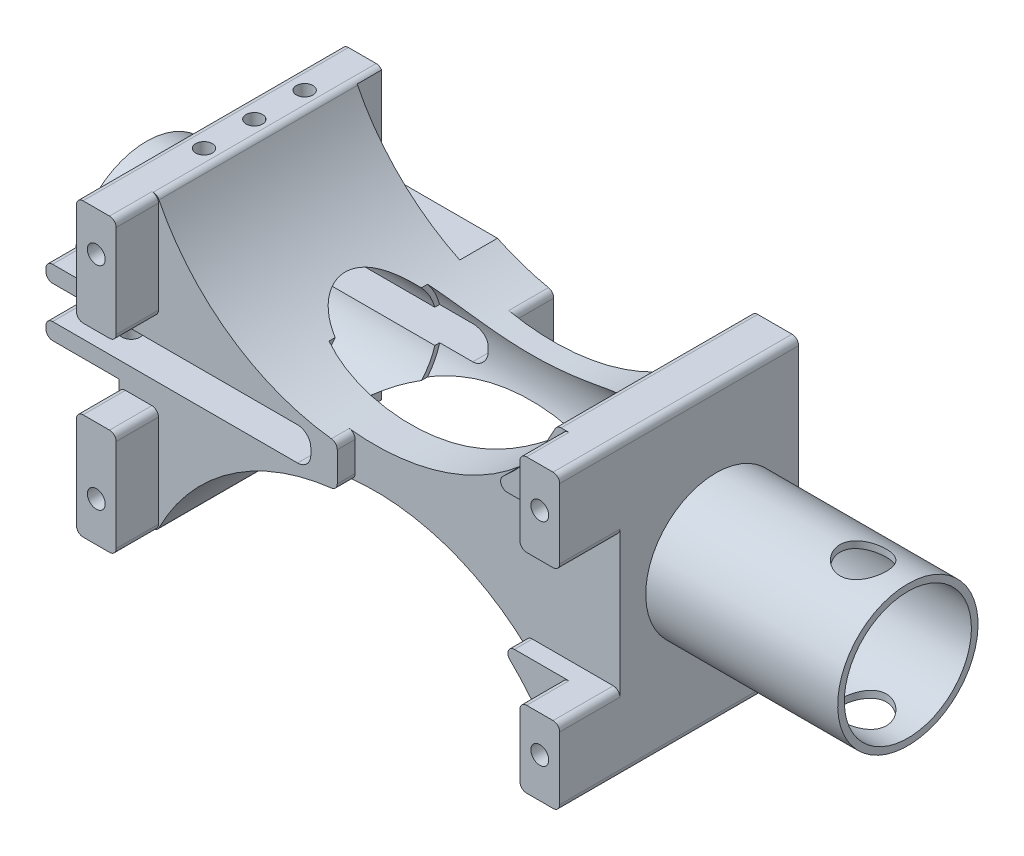
SolidWorks part; units mm, degrees
material "6061 合金"
ref_plane "前视基准面" through (0, 0, 0) normal (0, 0, 1) x (1, 0, 0)
ref_plane "上视基准面" through (0, 0, 0) normal (0, 1, 0) x (1, 0, 0)
ref_plane "右视基准面" through (0, 0, 0) normal (1, 0, 0) x (0, 0, -1)
other "Configuration Table"
sketch "草图1" plane through (0, 0, 0) normal (0, 0, 1) x (1, 0, 0)
  line L0 (0, 0) -> (36.5, 0) construction
  line L1 (-36.5, 22) -> (36.5, 22)
  line L2 (-36.5, 22) -> (-36.5, -22)
  line L3 (-36.5, -22) -> (36.5, -22)
  line L4 (36.5, 22) -> (36.5, -22)
  line L5 (-36.5, 22) -> (36.5, -22) construction
  line L6 (-36.5, -22) -> (36.5, 22) construction
  circle A0 centre (-0.5, 36.5) radius 33.5
  circle A1 centre (-0.5, -36.5) radius 33.5
  point P0 (0, 0)
  dimension "D4" = 67
  dimension "D5" = 37
  dimension "D1" = 44
  dimension "D2" = 73
  dimension "D3" = 73
extrude "凸台-拉伸1" add sketch "草图1" along normal blind 40 contours L3 A1 L4 L1 A0 L2
sketch "草图2" plane through (36.5, 0, 0) normal (1, 0, 0) x (0, 0, -1)
  line L1 (0, 22) -> (0, -22) construction
  circle A0 centre (-22.8, 0) radius 9.6
  dimension "D1" = 19.2
  dimension "D2" = 22.8
sketch "草图3" plane through (-36.5, 0, 0) normal (-1, 0, 0) x (0, 0, 1)
  circle A0 centre (22.8, 0) radius 8.9
  dimension "D1" = 17.8
extrude "切除-拉伸1" cut sketch "草图3" against normal through all
sketch "草图4" plane through (0, 0, 40) normal (0, 0, 1) x (1, 0, 0)
  line L0 (-7.5, -2.5) -> (-36.5, -2.5)
  line L1 (-7.5, -2.5) -> (-7.5, 2.5)
  line L2 (-36.5, -2.5) -> (-36.5, 2.5)
  line L3 (-7.5, 2.5) -> (-36.5, 2.5)
  line L4 (-7.5, -2.5) -> (-36.5, 2.5) construction
  line L5 (-36.5, -2.5) -> (-7.5, 2.5) construction
  line L6 (-36.5, 22) -> (-36.5, -22) construction
  point P1 (-22, 0)
  dimension "D1" = 5
  dimension "D2" = 29
extrude "切除-拉伸2" cut sketch "草图4" against normal through all
fillet "圆角1" radius 2 4 edges at (-7.5, -2.5, 7.1292) (-7.5, 2.5, 7.1292) (-7.5, -2.5, 35.6708) (-7.5, 2.5, 35.6708)
extrude "切除-拉伸3" cut sketch "草图2" against normal blind 51
sketch "草图5" plane through (0, 0, 0) normal (0, 0, -1) x (-1, 0, 0)
  line L0 (-36.5, 22) -> (-36.5, -22) construction
  line L1 (36.5, 22) -> (36.5, 2.5) construction
  line L2 (36.5, -2.5) -> (36.5, -22) construction
  circle A0 centre (-31.5, 10) radius 1.6
  circle A1 centre (-31.5, -10) radius 1.6
  circle A2 centre (33.5, 10) radius 1.6
  circle A3 centre (33.5, -10) radius 1.6
  dimension "D4" = 3.2
  dimension "D5" = 3.2
  dimension "D6" = 3.2
  dimension "D7" = 3.2
  dimension "D1" = 20
  dimension "D2" = 10
  dimension "D3" = 5
  dimension "D8" = 20
  dimension "D9" = 3
  dimension "D10" = 3
extrude "切除-拉伸4" [suppressed] cut sketch "草图5" against normal through all
sketch "草图6" plane through (0, 0, 0) normal (0, 0, -1) x (-1, 0, 0)
  line L0 (36.5, 22) -> (30.5, 22)
  line L1 (36.5, 22) -> (30.6993, 22) construction
  line L2 (30.5, 22) -> (30.5, 8.3)
  line L3 (30.5, 6.3) -> (11.32, 6.3)
  line L4 (11.32, 6.3) -> (11.32, 22)
  line L5 (11.32, 22) -> (30.5, 22)
  line L6 (0, 0) -> (13.8076, 0) construction
  line L7 (11.32, -22) -> (30.5, -22)
  line L8 (11.32, -6.3) -> (11.32, -22)
  line L9 (30.5, -6.3) -> (11.32, -6.3)
  line L10 (30.5, -22) -> (30.5, -8.3)
  line L11 (36.5, -22) -> (30.5, -22)
  arc A0 (30.5, -8.3) -> (30.5, -6.3) centre (30.5, -7.3) ccw
  arc A1 (30.5, 6.3) -> (30.5, 8.3) centre (30.5, 7.3) ccw
  line M16 (36.5, 22) -> (30.6993, 22)
  arc M17 (30.6993, 22) -> (-29.6993, 22) centre (0.5, 36.5) cw
  arc M21 (-29.6993, -22) -> (30.6993, -22) centre (0.5, -36.5) cw
  line M22 (30.6993, -22) -> (36.5, -22)
  dimension "D3" = 2
  dimension "D4" = 2
  dimension "D1" = 6
  dimension "D2" = 12.6
extrude "切除-拉伸5" cut sketch "草图6" against normal blind 10 contours L3 A1 L2 L4 M16 M17 | L10 A0 L9 L8 M21 M22
sketch "草图7" plane through (-36.5, 0, 0) normal (-1, 0, 0) x (0, 0, 1)
  circle A1 centre (22.8, 0) radius 11
  circle A2 centre (22.8, 0) radius 8.9
  dimension "D1" = 22
  dimension "D2" = 17.8
extrude "凸台-拉伸2" add sketch "草图7" along normal blind 13
chamfer "倒角1" distance 1.71 angle 45 1 edges at (-49.5, -8.9, 22.8)
sketch "草图9" plane through (-36.5, 0, 0) normal (1, 0, 0) x (0, 0, -1)
  line L1 (-19.4773, 2.5) -> (-41.3454, 2.5)
  line L2 (-19.4773, 2.5) -> (-19.4773, -2.5)
  line L3 (-19.4773, -2.5) -> (-41.3454, -2.5)
  line L4 (-41.3454, 2.5) -> (-41.3454, -2.5)
  line L5 (-19.4773, 2.5) -> (-41.3454, -2.5) construction
  line L6 (-19.4773, -2.5) -> (-41.3454, 2.5) construction
  point P0 (-30.4114, 0)
extrude "切除-拉伸6" cut sketch "草图9" against normal blind 13
sketch "草图10" plane through (-36.5, 0, 0) normal (-1, 0, 0) x (0, 0, 1)
  line L0 (22.8, 0) -> (46.6007, 0) construction
  line L1 (40, 5) -> (32.598, 5)
  line L2 (40, 22) -> (40, 2.5) construction
  line L3 (40, -5) -> (32.598, -5)
  line L4 (40, -2.5) -> (40, -22) construction
  line L5 (40, 5) -> (40, 2.5)
  line L6 (40, 2.5) -> (33.5121, 2.5)
  line L7 (33.5121, 2.5) -> (40, 2.5) construction
  line L8 (33.5121, -2.5) -> (40, -2.5)
  line L9 (40, -2.5) -> (40, -5)
  arc A1 (33.5121, 2.5) -> (33.5121, -2.5) centre (22.8, 0) ccw construction
  arc A2 (33.5121, 2.5) -> (32.598, 5) centre (22.8, 0) ccw
  arc A3 (32.598, -5) -> (33.5121, -2.5) centre (22.8, 0) ccw
  dimension "D1" = 5
  dimension "D2" = 5
extrude "凸台-拉伸6" add sketch "草图10" along normal blind 11
sketch "草图11" plane through (36.5, 0, 0) normal (1, 0, 0) x (0, 0, -1)
  circle A0 centre (-22.8, 0) radius 9.6
  circle A1 centre (-22.8, 0) radius 10.6
  dimension "D1" = 19.2
  dimension "D2" = 21.2
extrude "凸台-拉伸7" add sketch "草图11" along normal blind 29
sketch "草图12" plane through (0, 0, 0) normal (0, 1, 0) x (1, 0, 0)
  line L0 (65.5, -22.8) -> (36.5, -22.8) construction
  line L1 (65.5, -33.4) -> (65.5, -12.2) construction
  line L2 (36.5, -40) -> (36.5, 0) construction
  circle A0 centre (58.75, -22.8) radius 3.5
  dimension "D2" = 7
  dimension "D1" = 6.75
extrude "切除-拉伸7" cut sketch "草图12" against normal blind 13 and the other way blind 13
sketch "草图13" plane through (-36.5, 0, 0) normal (-1, 0, 0) x (0, 0, 1)
  line L1 (-4.3, -20) -> (4.3, -20)
  line L2 (-4.3, -20) -> (-4.3, 20)
  line L3 (-4.3, 20) -> (4.3, 20)
  line L4 (4.3, -20) -> (4.3, 20)
  line L5 (-4.3, -20) -> (4.3, 20) construction
  line L6 (-4.3, 20) -> (4.3, -20) construction
  arc A0 (31.3417, 2.5) -> (31.3417, -2.5) centre (22.8, 0) ccw construction
  point P0 (0, 0)
  dimension "D2" = 18.5
  dimension "D1" = 40
extrude "切除-拉伸8" cut sketch "草图13" against normal through all
sketch "草图14" plane through (-36.5, 0, 0) normal (-1, 0, 0) x (0, 0, 1)
  line L0 (4.3, 0.5) -> (4.3, -0.5) construction
  line L1 (2.3, -22) -> (6.3, -22)
  line L2 (2.3, -22) -> (2.3, -6.3)
  line L3 (2.3, 22) -> (6.3, 22)
  line L4 (6.3, -22) -> (6.3, -6.3)
  line L5 (2.3, -22) -> (6.3, 22) construction
  line L6 (2.3, 22) -> (6.3, -22) construction
  line L7 (40, 22) -> (0, 22) construction
  line L8 (4.3, 2.5) -> (4.3, 20) construction
  line L9 (6.3, 6.3) -> (6.3, 22)
  line L10 (2.3, -6.3) -> (6.3, -6.3)
  line L12 (2.3, 6.3) -> (6.3, 6.3)
  line L14 (2.3, -6.3) -> (6.3, 6.3) construction
  line L15 (2.3, 6.3) -> (6.3, -6.3) construction
  line L16 (2.3, 6.3) -> (2.3, 22)
  point P0 (4.3, 0)
  point P11 (4.3, 0)
  dimension "D1" = 2
  dimension "D2" = 12.6
extrude "切除-拉伸9" cut sketch "草图14" against normal blind 10
hole_wizard "M3x0.5 螺纹孔1" positions "草图15" profile "草图16" tap size "M3x0.5" standard "BSI"
sketch "草图15" plane through (0, 22, 0) normal (0, 1, 0) x (1, 0, 0)
  line L0 (-30.6993, -6.3) -> (-36.5, -6.3) construction
  point P0 (-33.2275, -15.2)
  point P2 (-33.2275, -22.8)
  point P4 (-33.2275, -30.4)
  dimension "D1" = 8.9
  dimension "D2" = 7.6
  dimension "D3" = 7.6
sketch "草图16" plane through (-33.2275, 22, 15.2) normal (1, 0, 0) x (0, 0, 1)
  line L0 (0, 0) -> (0, 6.7511)
  line L1 (0, 6.7511) -> (1.25, 6)
  line L2 (1.25, 6) -> (1.25, 0)
  line L5 (1.25, 0) -> (0, 0)
  line L10 (0, 6.7511) -> (-1.25, 6) construction
  line L11 (0, -6.35) -> (0, 107.95) construction
  dimension "螺纹孔钻头直径" = 2.5
  dimension "螺纹孔钻头深度" = 6
  dimension "导头角度" = 118
cosmetic thread "孔螺蚊线1" parameters "D1"=6, "D2"=3
cosmetic thread "孔螺蚊线2" parameters "D1"=6, "D2"=3
cosmetic thread "孔螺蚊线3" parameters "D1"=6, "D2"=3
sketch "草图17" plane through (36.5, 0, 0) normal (1, 0, 0) x (0, 0, -1)
  line L0 (-4.3, 20) -> (-4.3, -20) construction
  line L1 (1.7, 22) -> (-10.3, 22)
  line L2 (1.7, 22) -> (1.7, -22)
  line L3 (1.7, -22) -> (-10.3, -22)
  line L4 (-10.3, 22) -> (-10.3, -22)
  line L5 (1.7, 22) -> (-10.3, -22) construction
  line L6 (1.7, -22) -> (-10.3, 22) construction
  line L7 (-40, -22) -> (0, -22) construction
  circle A0 centre (-22.8, 0) radius 9.6 construction
  point P0 (-4.3, 0)
  dimension "D1" = 12.5
extrude "切除-拉伸10" cut sketch "草图17" against normal blind 37
sketch "草图18" plane through (0, 0, 10.3) normal (0, 0, -1) x (-1, 0, 0)
  line L0 (-36.5, 10.6) -> (-36.5, -10.6) construction
  line L2 (-26.8, 17.0845) -> (-26.8, -17.0845)
  line L4 (-22.8, 12.4301) -> (-22.8, -12.4301)
  line L5 (-26.6103, 16.8205) -> (-23.3983, -13.024) construction
  line L6 (-26.6103, -16.8205) -> (-23.3983, 13.024) construction
  arc A0 (-29.6993, 22) -> (0.5, 3) centre (0.5, 36.5) ccw construction
  arc A1 (0.5, -3) -> (-29.6993, -22) centre (0.5, -36.5) ccw construction
  arc A2 (-26.8, 17.0845) -> (-22.8, 12.4301) centre (0.5, 36.5) ccw
  arc A3 (-22.8, -12.4301) -> (-26.8, -17.0845) centre (0.5, -36.5) ccw
  point P0 (-24.8, 0)
  dimension "D1" = 13.7
extrude "凸台-拉伸8" add sketch "草图18" along normal blind 3
fillet "圆角2" radius 1 4 edges at (22.8, 12.4301, 8.8) (26.8, 17.0845, 8.8) (22.8, -12.4301, 8.8) (26.8, -17.0845, 8.8)
sketch "草图19" plane through (36.5, 0, 0) normal (1, 0, 0) x (0, 0, -1)
  line L1 (-42.7, 9.5) -> (-37.3, 9.5)
  line L2 (-42.7, 9.5) -> (-42.7, -10.5)
  line L3 (-42.7, -10.5) -> (-37.3, -10.5)
  line L4 (-37.3, 9.5) -> (-37.3, -10.5)
  line L5 (-42.7, 9.5) -> (-37.3, -10.5) construction
  line L6 (-42.7, -10.5) -> (-37.3, 9.5) construction
  circle A0 centre (-22.8, 0) radius 9.6 construction
  point P0 (-40, -0.5)
  dimension "D1" = 20
  dimension "D2" = 14.5
extrude "切除-拉伸11" cut sketch "草图19" against normal blind 40
sketch "草图21" plane through (0, 0, 40) normal (0, 0, 1) x (1, 0, 0)
  line L0 (36.5, -10.5) -> (36.5, -22)
  line L1 (36.5, -10.5) -> (30.5, -10.5)
  line L2 (36.5, -22) -> (30.5, -22)
  line L3 (30.5, -10.5) -> (30.5, -22)
  line L4 (36.5, 22) -> (36.5, 9.5)
  line L5 (36.5, 22) -> (30.5, 22)
  line L6 (36.5, 9.5) -> (30.5, 9.5)
  line L7 (30.5, 22) -> (30.5, 9.5)
  line L8 (-36.5, 22) -> (-36.5, 6)
  line L9 (-36.5, 22) -> (-30.5, 22)
  line L10 (-36.5, 6) -> (-30.5, 6)
  line L11 (-30.5, 22) -> (-30.5, 6)
  line L12 (-36.5, 22) -> (-36.5, 5) construction
  line L13 (-36.5, -22) -> (-36.5, -6)
  line L14 (-36.5, -22) -> (-30.5, -22)
  line L15 (-36.5, -6) -> (-30.5, -6)
  line L16 (-30.5, -22) -> (-30.5, -6)
  line L17 (-36.5, -5) -> (-36.5, -22) construction
  line L19 (0, 0) -> (-61.9022, 0) construction
  dimension "D1" = 12
  dimension "D2" = 6
  dimension "D3" = 6
  dimension "D4" = 6
  dimension "D5" = 6
  dimension "D6" = 6
extrude "凸台-拉伸9" add sketch "草图21" along normal blind 6.4
sketch "草图22" plane through (0, 0, 4.3) normal (0, 0, -1) x (-1, 0, 0)
  line L0 (0.5, 3) -> (0.5, -3) construction
  line L1 (-5.5, 6.6112) -> (6.5, 6.6112)
  line L2 (-5.5, 6.6112) -> (-5.5, -6.6112)
  line L3 (-5.5, -6.6112) -> (6.5, -6.6112)
  line L4 (6.5, 6.6112) -> (6.5, -6.6112)
  line L5 (-5.5, 6.6112) -> (6.5, -6.6112) construction
  line L6 (-5.5, -6.6112) -> (6.5, 6.6112) construction
  line L7 (0.5, 3) -> (0.5, -3) construction
  point P0 (0.5, 0)
  dimension "D1" = 6
extrude "切除-拉伸12" cut sketch "草图22" against normal up to surface (6 mm away) up to face at (15.4288, 0, 10.3)
fillet "圆角3" radius 1 27 edges at (-36.5, 22, 26.35) (29.6993, 22, 25.15) (-47.5, 5, 36.299) (-47.5, 2.5, 36.7561) (-47.5, -2.5, 36.7561) (-47.5, -5, 36.299) (20.6246, -10.5, 38.65) (19.3305, 9.5, 38.65) (-3.5, -3.1346, 38.65) (-3.5, 3.1346, 38.65) (36.5, -10.5, 41.85) (36.5, 9.5, 41.85) (30.5, -10.5, 43.2) (30.5, -22, 43.2) (30.5, 22, 43.2) (30.5, 9.5, 43.2) (-30.5, 22, 43.2) (-36.5, 6, 43.2) (-30.5, 6, 43.2) (-30.5, -22, 43.2) (-30.5, -6, 43.2) (-36.5, -6, 43.2) (-6.5, 3.5417, 7.3) (-6.5, -3.5417, 7.3) (36.5, -22, 28.35) (29.6993, -22, 25.15) (36.5, 22, 28.35)
hole_wizard "M3 螺纹孔1" positions "草图23" profile "草图24" tap size "M3" standard "GB"
sketch "草图23" plane through (0, 0, 46.4) normal (0, 0, 1) x (1, 0, 0)
  line L0 (-36.5, -7) -> (-36.5, -22) construction
  line L1 (-36.5, 21) -> (-36.5, 7) construction
  point P0 (-33.5, -16)
  point P2 (-33.5, 16)
  dimension "D1" = 32
  dimension "D2" = 16
  dimension "D3" = 3
  dimension "D4" = 3
sketch "草图24" plane through (-33.5, -16, 46.4) normal (1, 0, 0) x (0, -1, 0)
  line L0 (0, 0) -> (0, 8.3112)
  line L1 (0, 8.3112) -> (1.35, 7.5)
  line L2 (1.35, 7.5) -> (1.35, 0)
  line L5 (1.35, 0) -> (0, 0)
  line L10 (0, 8.3112) -> (-1.35, 7.5) construction
  line L11 (0, -6.35) -> (0, 107.95) construction
  dimension "螺纹孔钻头直径" = 2.7
  dimension "螺纹孔钻头深度" = 7.5
  dimension "导头角度" = 118
cosmetic thread "孔螺蚊线4" parameters "D1"=6, "D2"=3
cosmetic thread "孔螺蚊线5" parameters "D1"=6, "D2"=3
hole_wizard "M3 螺纹孔2" positions "草图25" profile "草图26" tap size "M3" standard "GB"
sketch "草图25" plane through (0, 0, 46.4) normal (0, 0, 1) x (1, 0, 0)
  line L2 (36.5, 10.5) -> (36.5, 21) construction
  line L3 (36.5, -21) -> (36.5, -11.5) construction
  point P0 (33.5, 16)
  point P2 (33.5, -16)
  dimension "D1" = 32
  dimension "D2" = 16
  dimension "D3" = 3
  dimension "D4" = 3
sketch "草图26" plane through (33.5, 16, 46.4) normal (1, 0, 0) x (0, -1, 0)
  line L0 (0, 0) -> (0, 8.3112)
  line L1 (0, 8.3112) -> (1.35, 7.5)
  line L2 (1.35, 7.5) -> (1.35, 0)
  line L5 (1.35, 0) -> (0, 0)
  line L10 (0, 8.3112) -> (-1.35, 7.5) construction
  line L11 (0, -6.35) -> (0, 107.95) construction
  dimension "螺纹孔钻头直径" = 2.7
  dimension "螺纹孔钻头深度" = 7.5
  dimension "导头角度" = 118
cosmetic thread "孔螺蚊线6" parameters "D1"=6, "D2"=3
cosmetic thread "孔螺蚊线7" parameters "D1"=6, "D2"=3
sketch "草图27" plane through (0, 0, 6.3) normal (0, 0, -1) x (-1, 0, 0)
  line L0 (30.5, -21.5919) -> (30.5, -8.3) construction
  point P0 (33.5032, 16)
  point P2 (33.5032, -16)
  dimension "D1" = 3.0032
  dimension "D2" = 32
  dimension "D3" = 16
hole_wizard "M3 螺纹孔3" positions "草图27" profile "草图28" tap size "M3" standard "GB"
sketch "草图28" plane through (-33.5032, 16, 6.3) normal (1, 0, 0) x (0, 1, 0)
  line L0 (0, 0) -> (0, 8.3112)
  line L1 (0, 8.3112) -> (1.35, 7.5)
  line L2 (1.35, 7.5) -> (1.35, 0)
  line L5 (1.35, 0) -> (0, 0)
  line L10 (0, 8.3112) -> (-1.35, 7.5) construction
  line L11 (0, -6.35) -> (0, 107.95) construction
  dimension "螺纹孔钻头直径" = 2.7
  dimension "螺纹孔钻头深度" = 7.5
  dimension "导头角度" = 118
cosmetic thread "孔螺蚊线8" parameters "D1"=6, "D2"=3
cosmetic thread "孔螺蚊线9" parameters "D1"=6, "D2"=3
hole_wizard "M3 螺纹孔4" positions "草图29" profile "草图30" tap size "M3" standard "GB"
sketch "草图29" plane through (0, 0, 10.3) normal (0, 0, -1) x (-1, 0, 0)
  line L0 (-36.5, 21) -> (-36.5, -21) construction
  point P0 (-33.5, 16)
  point P2 (-33.5, -16)
  dimension "D1" = 32
  dimension "D2" = 16
  dimension "D3" = 3
  dimension "D4" = 3
sketch "草图30" plane through (33.5, 16, 10.3) normal (1, 0, 0) x (0, 1, 0)
  line L0 (0, 0) -> (0, 8.3112)
  line L1 (0, 8.3112) -> (1.35, 7.5)
  line L2 (1.35, 7.5) -> (1.35, 0)
  line L5 (1.35, 0) -> (0, 0)
  line L10 (0, 8.3112) -> (-1.35, 7.5) construction
  line L11 (0, -6.35) -> (0, 107.95) construction
  dimension "螺纹孔钻头直径" = 2.7
  dimension "螺纹孔钻头深度" = 7.5
  dimension "导头角度" = 118
cosmetic thread "孔螺蚊线10" parameters "D1"=6, "D2"=3
cosmetic thread "孔螺蚊线11" parameters "D1"=6, "D2"=3
mirror "镜向1" about plane through (0, 0, 0) normal (0, 1, 0) of "M3x0.5 螺纹孔1"
sketch "草图31" plane through (-36.5, 0, 0) normal (-1, 0, 0) x (0, 0, 1)
  line L1 (-4.3, 24.2023) -> (4.3, 24.2023)
  line L2 (-4.3, 24.2023) -> (-4.3, -24.2023)
  line L3 (-4.3, -24.2023) -> (4.3, -24.2023)
  line L4 (4.3, 24.2023) -> (4.3, -24.2023)
  line L5 (-4.3, 24.2023) -> (4.3, -24.2023) construction
  line L6 (-4.3, -24.2023) -> (4.3, 24.2023) construction
  point P0 (0, 0)
extrude "切除-拉伸13" cut sketch "草图31" against normal blind 10
fillet "圆角4" radius 1 3 edges at (-30.6993, 22, 23.15) (-36.5, -22, 26.35) (-30.6993, -22, 23.15)
hole_wizard "M3 螺纹孔5" positions "草图32" profile "草图33" tap size "M3" standard "GB" end condition through all
sketch "草图32" plane through (0, 5, 0) normal (0, 1, 0) x (1, 0, 0)
  line L0 (-35.5, -6.3) -> (-35.5, -46.4) construction
  line L2 (-46.5, -40) -> (-36.5, -40) construction
  point P0 (-39.2, -35.45)
  point P2 (-44.7, -35.45)
  dimension "D1" = 5.5
  dimension "D2" = 3.7
  dimension "D3" = 4.55
  dimension "D4" = 4.55
sketch "草图33" plane through (-39.2, 5, 35.45) normal (1, 0, 0) x (0, 0, 1)
  line L0 (0, 0) -> (0, 27)
  line L1 (0, 27) -> (1.35, 27)
  line L2 (1.35, 27) -> (1.35, 0)
  line L5 (1.35, 0) -> (0, 0)
  line L11 (0, -6.35) -> (0, 107.95) construction
  dimension "通孔螺纹孔钻头直径" = 2.7
  dimension "通孔螺纹孔钻头深度" = 27
cosmetic thread "孔螺蚊线12" parameters "D2"=3
cosmetic thread "孔螺蚊线13" parameters "D2"=3
